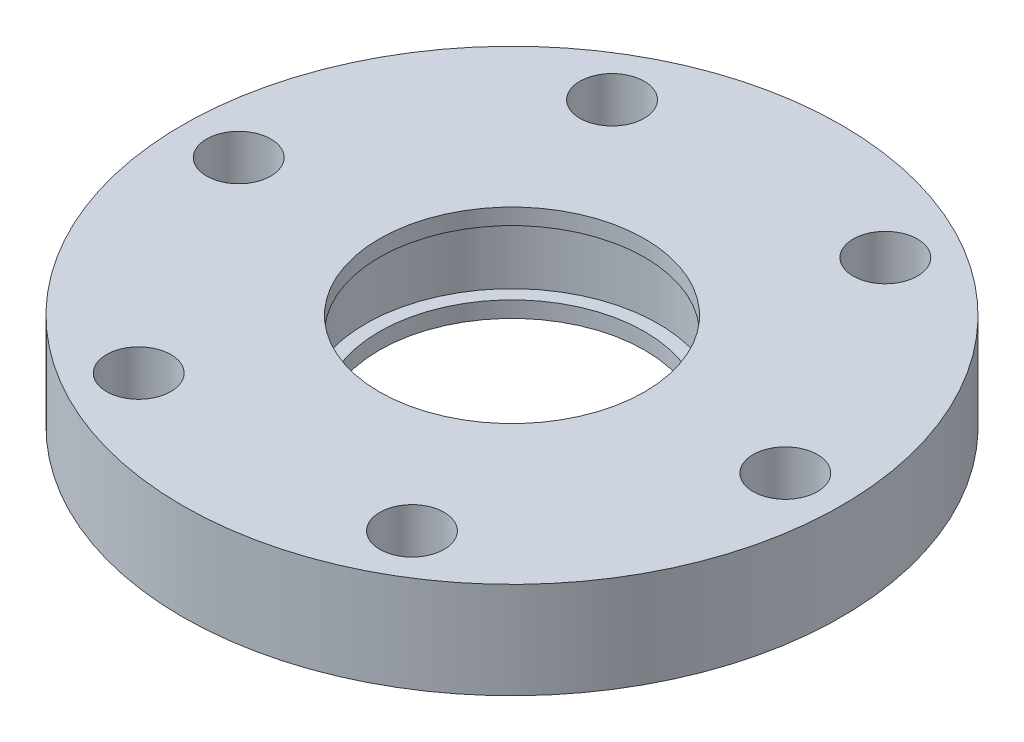
SolidWorks part; units mm, degrees
ref_plane "Front Plane" through (0, 0, 0) normal (0, 0, 1) x (1, 0, 0)
ref_plane "Top Plane" through (0, 0, 0) normal (0, 1, 0) x (1, 0, 0)
ref_plane "Right Plane" through (0, 0, 0) normal (1, 0, 0) x (0, 0, -1)
sketch "Sketch1" plane through (0, 0, 0) normal (0, 1, 0) x (1, 0, 0)
  circle A0 centre (0, 0) radius 17 construction
  circle A1 centre (17, 0) radius 2
  circle A2 centre (8.5, -14.7224) radius 2
  circle A3 centre (-8.5, -14.7224) radius 2
  circle A4 centre (-17, 0) radius 2
  circle A5 centre (-8.5, 14.7224) radius 2
  circle A6 centre (8.5, 14.7224) radius 2
  circle A7 centre (0, 0) radius 20.5
  circle A8 centre (0, 0) radius 8.25
  point P17 (0, 0)
  dimension "D1" = 34
  dimension "D2" = 4
  dimension "D5" = 16.5
  dimension "D4" = 3.5
  dimension "D3" = 6
extrude "Boss-Extrude1" add sketch "Sketch1" along normal mid plane 6
sketch "Sketch2" plane through (0, 0, 0) normal (0, 1, 0) x (1, 0, 0)
  circle A0 centre (0, 0) radius 9.1
  dimension "D1" = 18.2
extrude "Cut-Extrude1" cut sketch "Sketch2" against normal mid plane 4
sketch "Sketch3" plane through (0, -3, 0) normal (0, 1, 0) x (1, 0, 0)
  circle A0 centre (0, 0) radius 15
  circle A1 centre (0, 0) radius 19
  circle A2 centre (8.5, 14.7224) radius 2 construction
extrude "Boss-Extrude2" add sketch "Sketch3" along normal blind 1
equation "\"RotorRadius\"= 25mm"
equation "\"Eccentricity\"= 1.00mm"
equation "\"RollerRadius\"= 1.5mm"
equation "\"GearRatio\"= 20"
equation "\"RollerCount\"=\"GearRatio\" + 1"
equation "\"RotorThickness\"= 6mm"
equation "\"OutputRollerRadius\"= 2mm"
equation "\"OutputRollerCount\"= 6"
equation "\"OutputRollerHoleCircleRadius\"=\"RotorRadius\"- 4 * \"OutputRollerRadius\""
equation "\"RotorGap\"= 0.5mm"
equation "\"D1@Sketch1\"=2*\"OutputRollerHoleCircleRadius\""
equation "\"D2@Sketch1\"=\"OutputRollerRadius\"*2"
equation "\"D1@Boss-Extrude1\"=\"RotorThickness\""
